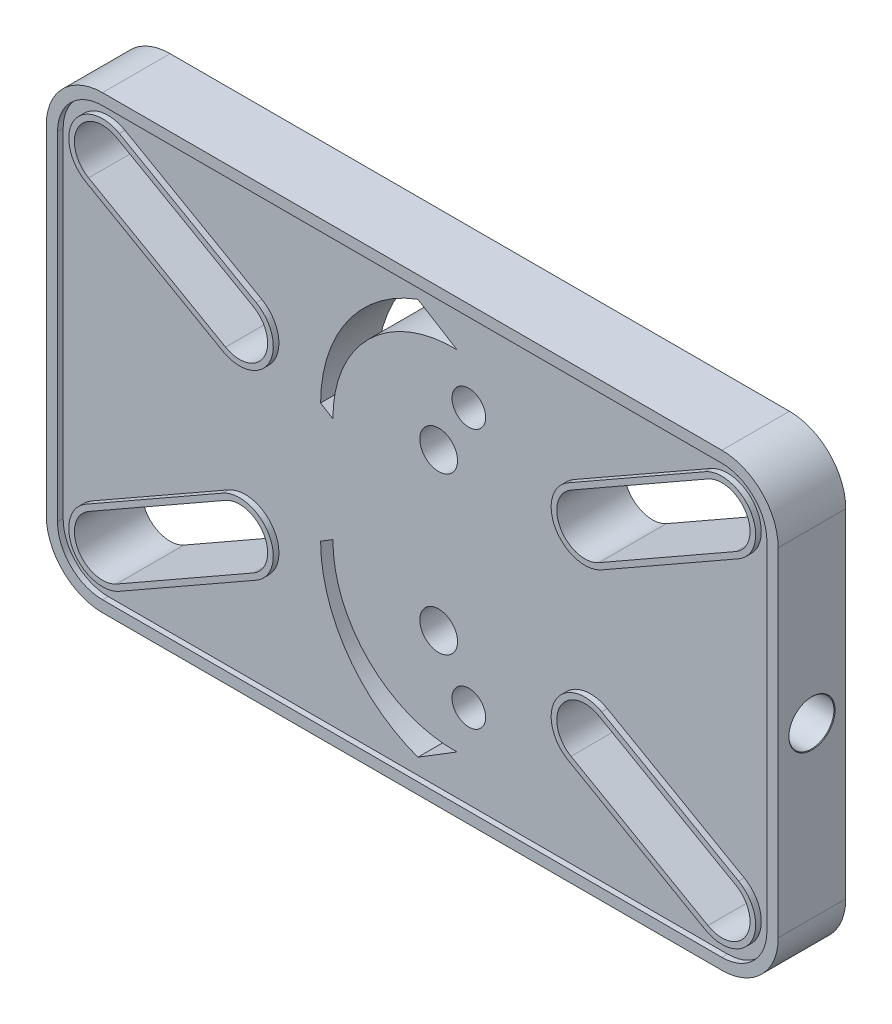
SolidWorks part; units mm, degrees
ref_plane "Front Plane" through (0, 0, 0) normal (0, 0, 1) x (1, 0, 0)
ref_plane "Top Plane" through (0, 0, 0) normal (0, 1, 0) x (1, 0, 0)
ref_plane "Right Plane" through (0, 0, 0) normal (1, 0, 0) x (0, 0, -1)
sketch "Sketch1" plane through (0, 0, 0) normal (0, 0, 1) x (1, 0, 0)
  line L0 (-27.5, 15) -> (-15.338, 8.0655) construction
  line L1 (-27.5, 20) -> (27.5, 20)
  line L2 (-32.5, 15) -> (-32.5, -15)
  line L3 (-27.5, -20) -> (27.5, -20)
  line L4 (32.5, 15) -> (32.5, -15)
  line L5 (-32.5, 20) -> (32.5, -20) construction
  line L6 (-32.5, -20) -> (32.5, 20) construction
  line L7 (-26.2617, 17.1718) -> (-14.0997, 10.2373)
  line L8 (-28.7383, 12.8282) -> (-16.5763, 5.8937)
  line L9 (0, 0) -> (-45.4568, 0) construction
  line L10 (0, 0) -> (0, 28.4945) construction
  line L11 (27.5, 15) -> (15.338, 8.0655) construction
  line L12 (26.2617, 17.1718) -> (14.0997, 10.2373)
  line L13 (28.7383, 12.8282) -> (16.5763, 5.8937)
  line L14 (27.5, -15) -> (15.338, -8.0655) construction
  line L15 (26.2617, -17.1718) -> (14.0997, -10.2373)
  line L16 (28.7383, -12.8282) -> (16.5763, -5.8937)
  line L17 (-27.5, -15) -> (-15.338, -8.0655) construction
  line L18 (-26.2617, -17.1718) -> (-14.0997, -10.2373)
  line L19 (-28.7383, -12.8282) -> (-16.5763, -5.8937)
  line L25 (-8.6382, 5.3158) -> (-7.5407, 4.6404)
  line L26 (0, 17.6077) -> (3.4818, 15.465)
  line L30 (-31.5, 15) -> (-31.5, -15)
  line L31 (-27.5, -19) -> (27.5, -19)
  line L32 (31.5, 15) -> (31.5, -15)
  line L33 (-27.5, 19) -> (27.5, 19)
  line L34 (-26.014, 17.6061) -> (-13.8521, 10.6717)
  line L35 (-28.986, 12.3939) -> (-16.824, 5.4594)
  line L36 (26.014, 17.6061) -> (13.8521, 10.6717)
  line L37 (28.986, 12.3939) -> (16.824, 5.4594)
  line L38 (26.014, -17.6061) -> (13.8521, -10.6717)
  line L39 (28.986, -12.3939) -> (16.824, -5.4594)
  line L48 (-26.014, -17.6061) -> (-13.8521, -10.6717)
  line L49 (-28.986, -12.3939) -> (-16.824, -5.4594)
  line L50 (-8.6382, -5.3158) -> (-7.5407, -4.6404)
  line L51 (0, -17.6077) -> (3.4818, -15.465)
  arc A0 (27.5, 20) -> (32.5, 15) centre (27.5, 15) cw
  arc A1 (27.5, -20) -> (32.5, -15) centre (27.5, -15) ccw
  arc A2 (-32.5, -15) -> (-27.5, -20) centre (-27.5, -15) ccw
  arc A3 (-27.5, 20) -> (-32.5, 15) centre (-27.5, 15) ccw
  arc A4 (-26.2617, 17.1718) -> (-28.7383, 12.8282) centre (-27.5, 15) ccw
  arc A5 (-16.5763, 5.8937) -> (-14.0997, 10.2373) centre (-15.338, 8.0655) ccw
  arc A6 (26.2617, 17.1718) -> (28.7383, 12.8282) centre (27.5, 15) cw
  arc A7 (16.5763, 5.8937) -> (14.0997, 10.2373) centre (15.338, 8.0655) cw
  arc A8 (26.2617, -17.1718) -> (28.7383, -12.8282) centre (27.5, -15) ccw
  arc A9 (16.5763, -5.8937) -> (14.0997, -10.2373) centre (15.338, -8.0655) ccw
  arc A10 (-26.2617, -17.1718) -> (-28.7383, -12.8282) centre (-27.5, -15) cw
  arc A11 (-16.5763, -5.8937) -> (-14.0997, -10.2373) centre (-15.338, -8.0655) cw
  arc A12 (-31.5, -15) -> (-27.5, -19) centre (-27.5, -15) ccw
  arc A13 (27.5, -19) -> (31.5, -15) centre (27.5, -15) ccw
  arc A14 (27.5, 19) -> (31.5, 15) centre (27.5, 15) cw
  arc A15 (-27.5, 19) -> (-31.5, 15) centre (-27.5, 15) ccw
  arc A16 (-16.824, 5.4594) -> (-13.8521, 10.6717) centre (-15.338, 8.0655) ccw
  arc A17 (-26.014, 17.6061) -> (-28.986, 12.3939) centre (-27.5, 15) ccw
  arc A18 (16.824, 5.4594) -> (13.8521, 10.6717) centre (15.338, 8.0655) cw
  arc A19 (26.014, 17.6061) -> (28.986, 12.3939) centre (27.5, 15) cw
  arc A20 (16.824, -5.4594) -> (13.8521, -10.6717) centre (15.338, -8.0655) ccw
  arc A21 (26.014, -17.6061) -> (28.986, -12.3939) centre (27.5, -15) ccw
  arc A22 (-16.824, -5.4594) -> (-13.8521, -10.6717) centre (-15.338, -8.0655) cw
  arc A23 (-26.014, -17.6061) -> (-28.986, -12.3939) centre (-27.5, -15) cw
  arc A24 (-8.6382, 5.3158) -> (0, 17.6077) centre (4.5272, 5.2449) cw
  arc A25 (-7.5407, 4.6404) -> (3.4818, 15.465) centre (3.195, 4.7328) cw
  circle A26 centre (4.5271, 11.5328) radius 1.4957
  circle A27 centre (1.8485, 6.9576) radius 1.6765
  circle A28 centre (4.5271, -11.5328) radius 1.4957
  arc A29 (-8.6382, -5.3158) -> (0, -17.6077) centre (4.5272, -5.2449) ccw
  arc A30 (-7.5407, -4.6404) -> (3.4818, -15.465) centre (3.195, -4.7328) ccw
  circle A31 centre (1.8485, -6.9576) radius 1.6765
  point P0 (0, 0)
  point P20 (-21.419, 11.5328)
  point P27 (21.419, 11.5328)
  point P35 (21.419, -11.5328)
  point P41 (-21.419, -11.5328)
  dimension "D3" = 5
  dimension "D1" = 65
  dimension "D2" = 40
  dimension "D4" = 5
  dimension "D5" = 14
  dimension "D6" = 1
  dimension "D7" = 0.5
extrude "Boss-Extrude2" add sketch "Sketch1" along normal mid plane 6 contours L1 A3 L2 A2 L3 A1 L4 A0 A15 L33 A14 L32 A13 L31 A12 L30 | A19 L36 A18 L37 L13 A7 L12 A6 | L34 A17 L35 A16 A5 L8 A4 L7 | A23 L48 A22 L49 L19 A11 L18 A10 | L38 A21 L39 A20 A9 L16 A8 L15 region at (0, 19.2368, 0) region at (-20.0435, 13.9452, 0) region at (29.9124, 16.3755, 0) region at (20.0435, -13.9452, 0) region at (-29.9124, -16.3755, 0)
extrude "Boss-Extrude3" add sketch "Sketch1<3>" along normal mid plane 5 contours L33 A15 L30 A12 L31 A13 L32 A14 L36 A19 L37 A18 A17 L34 A16 L35 A21 L38 A20 L39 L48 A23 L49 A22 region at (0.0699, 0, 0)
sketch "Sketch1<3>" plane through (0, 0, 0) normal (0, 0, 1) x (1, 0, 0) same geometry as "Sketch1"
sketch "Sketch4" plane through (-32.5, 0, 0) normal (-1, 0, 0) x (0, 0, 1)
  circle A0 centre (0, 0) radius 2
  dimension "D1" = 4
extrude "Cut-Extrude5" cut sketch "Sketch4" against normal through all
chamfer "Chamfer1" distance 0.05 angle 45 2 edges at (32.5, -2, 0) (-32.5, -2, 0)
